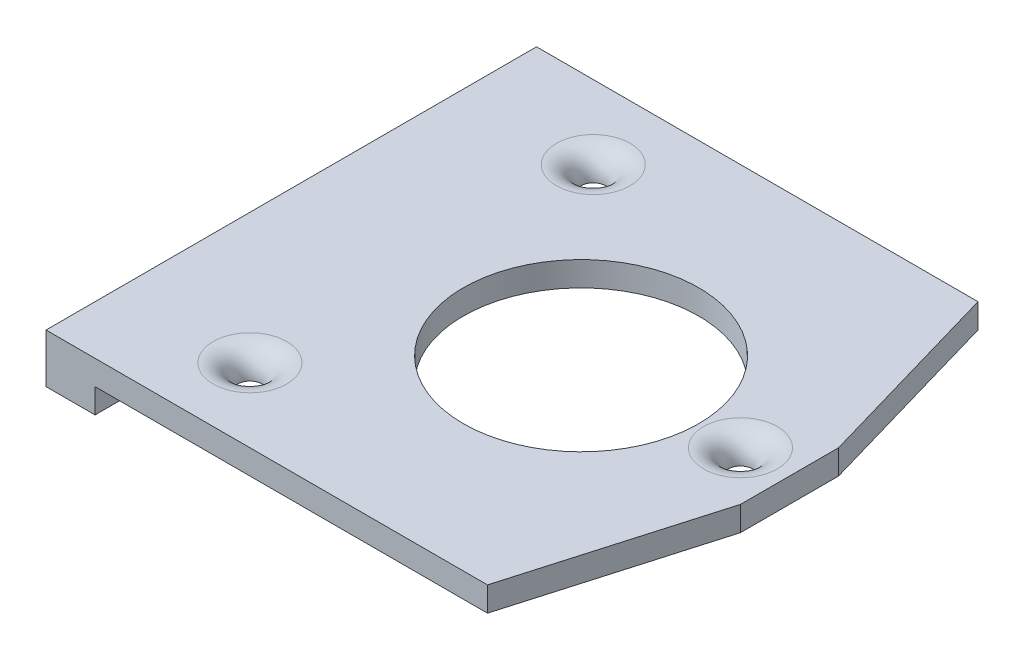
SolidWorks part; units mm, degrees
ref_plane "Front Plane" through (0, 0, 0) normal (0, 0, 1) x (1, 0, 0)
ref_plane "Top Plane" through (0, 0, 0) normal (0, 1, 0) x (1, 0, 0)
ref_plane "Right Plane" through (0, 0, 0) normal (1, 0, 0) x (0, 0, -1)
sketch "Sketch2" plane through (0, 0, 0) normal (0, 0, 1) x (1, 0, 0)
  line L0 (0, 0) -> (0, 63.9226) construction
sketch "Sketch3" plane through (0, 0, 0) normal (0, 1, 0) x (1, 0, 0)
  line L0 (0, 31.75) -> (0, -31.75)
  line L1 (0, 31.75) -> (50.8, 31.75)
  line L2 (0, -31.75) -> (50.8, -31.75)
  line L4 (0, 0) -> (-515.3919, 0) construction
  line L5 (10.525, 22.225) -> (10.525, -22.225) construction
  line L6 (1, 31.75) -> (1, -31.75) construction
  line L7 (10.525, 0) -> (51.8, 0) construction
  line L8 (58.15, 6.35) -> (50.8, 31.75)
  line L9 (58.15, 6.35) -> (58.15, -6.35)
  line L10 (50.8, -31.75) -> (58.15, -6.35)
  line L11 (50.8, 31.75) -> (50.8, -31.75) construction
  circle A2 centre (51.8, 0) radius 1.5875
  circle A3 centre (10.525, 22.225) radius 1.5875
  circle A4 centre (10.525, -22.225) radius 1.5875
  circle A7 centre (31.1625, 0) radius 15.24
  point P3 (0, 0)
  point P14 (10.525, 0)
  point P24 (58.15, 0)
  dimension "D6" = 9.525
  dimension "D4" = 30.48
  dimension "D7" = 3.175
  dimension "D8" = 50.8
  dimension "D9" = 12.7
  dimension "D1" = 63.5
  dimension "D2" = 50.8
  dimension "D3" = 1
  dimension "D5" = 9.525
  dimension "D10" = 6.35
extrude "Boss-Extrude1" add sketch "Sketch3" along normal blind 3.175
sketch "Sketch4" plane through (0, 0, 0) normal (-1, 0, 0) x (0, 0, 1)
  line L0 (-31.75, 3.175) -> (31.75, 3.175)
  line L1 (-31.75, 3.175) -> (-31.75, -3.175)
  line L2 (31.75, 3.175) -> (31.75, -3.175)
  line L3 (-31.75, -3.175) -> (31.75, -3.175)
  dimension "D1" = 6.35
extrude "Boss-Extrude2" add sketch "Sketch4" along normal blind 6.35
fillet "Fillet1" radius 3.175 3 edges at (10.525, 3.175, 23.8125) (51.8, 3.175, 1.5875) (10.525, 3.175, -20.6375)
